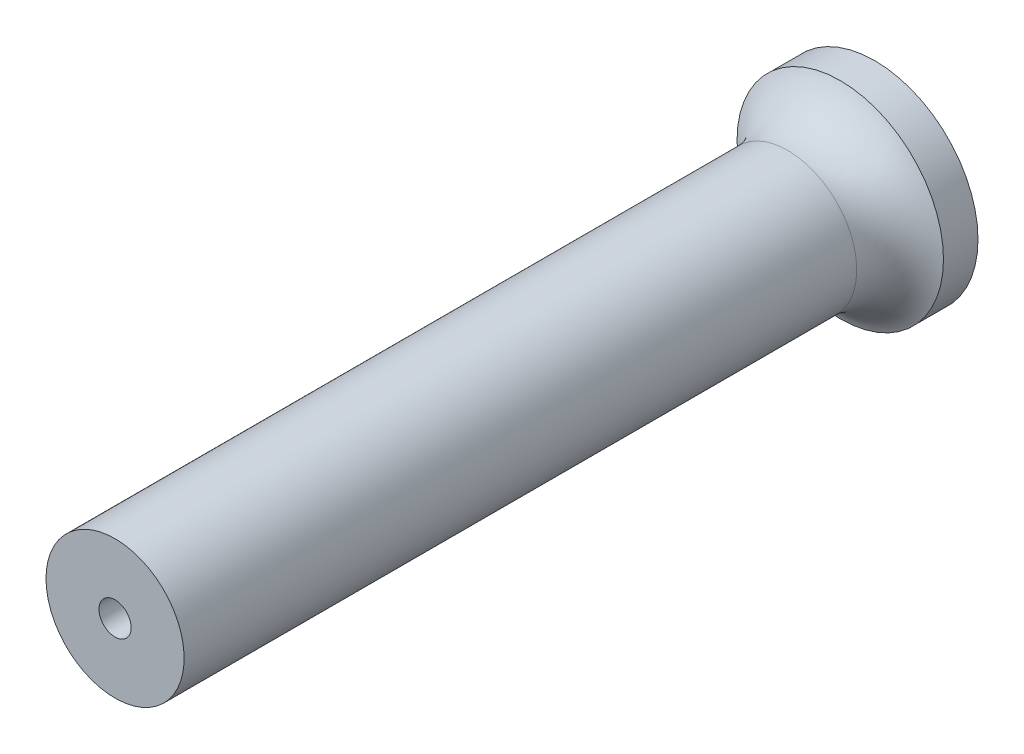
SolidWorks part; units mm, degrees
ref_plane "Спереди" through (0, 0, 0) normal (0, 0, 1) x (1, 0, 0)
ref_plane "Сверху" through (0, 0, 0) normal (0, 1, 0) x (1, 0, 0)
ref_plane "Справа" through (0, 0, 0) normal (1, 0, 0) x (0, 0, -1)
sketch "Эскиз1" plane through (0, 0, 0) normal (0, 0, 1) x (1, 0, 0)
  circle A1 centre (150.7717, 87.3525) radius 1.4
  circle A2 centre (150.7717, 87.3525) radius 8.966
  point P4 (0, 0)
  point P5 (0, 0)
  point P10 (0, 0)
  point P11 (0, 0)
  point P12 (150, 88.255)
extrude "Бобышка-Вытянуть1" add sketch "Эскиз1" along normal blind 3
sketch "Эскиз2" plane through (0, 0, 0) normal (0, 0, -1) x (-1, 0, 0)
  circle A0 centre (-150.7717, 87.3525) radius 1.4
  circle A1 centre (-150.7717, 87.3525) radius 6
  point P5 (0, 0)
extrude "Бобышка-Вытянуть2" add sketch "Эскиз2" against normal blind 66
fillet "Скругление1" radius 5 1 edges at (156.7717, 87.3525, 3)
